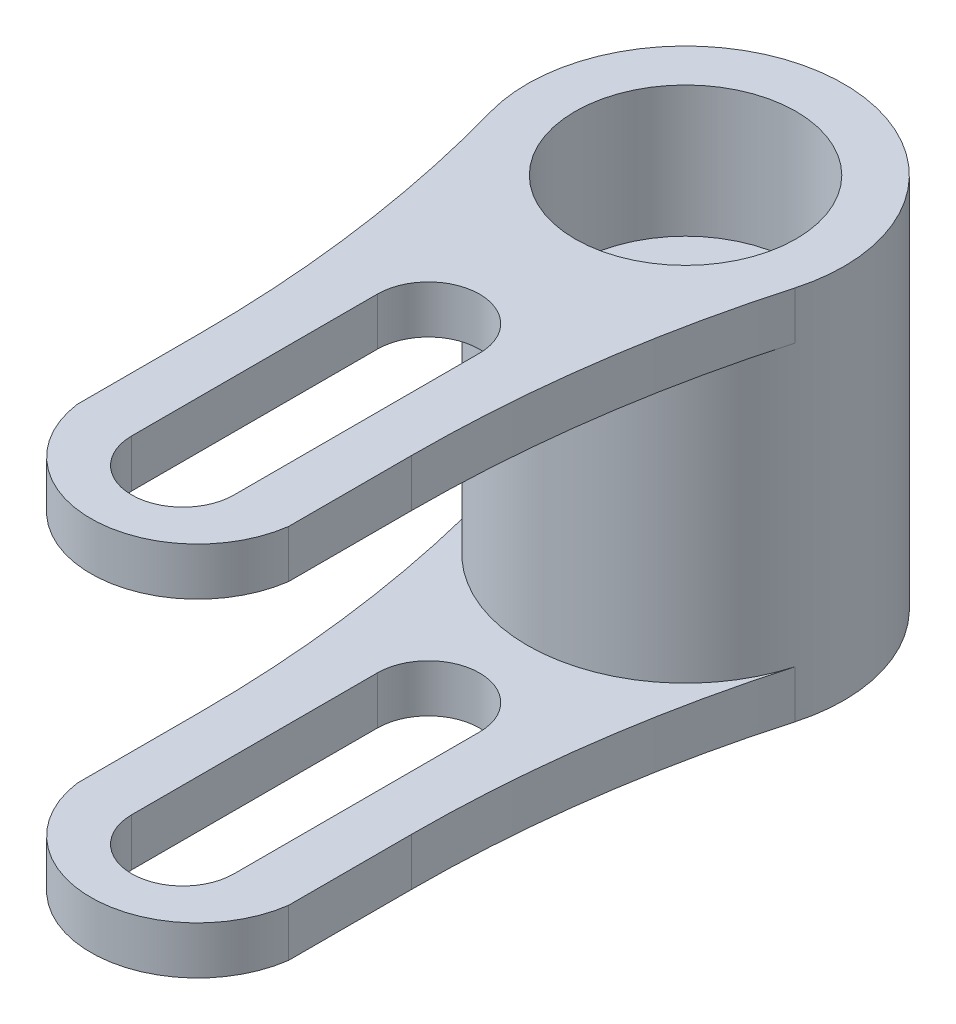
SolidWorks part; units mm, degrees
ref_plane "Front Plane" through (0, 0, 0) normal (0, 0, 1) x (1, 0, 0)
ref_plane "Top Plane" through (0, 0, 0) normal (0, 1, 0) x (1, 0, 0)
ref_plane "Right Plane" through (0, 0, 0) normal (1, 0, 0) x (0, 0, -1)
sketch "Sketch1" plane through (0, 0, 0) normal (0, 1, 0) x (1, 0, 0)
  line L0 (0, 5.8) -> (0, 4.05) construction
  line L1 (0, -9.425) -> (0, -18.425) construction
  line L2 (-3.875, -13.925) -> (-3.875, -18.425)
  line L3 (3.875, -18.425) -> (3.875, -13.925)
  line L4 (1.875, -9.425) -> (1.875, -18.425)
  line L5 (-1.875, -9.425) -> (-1.875, -18.425)
  line L6 (0, -7.55) -> (0, -5.8) construction
  line L7 (-3.875, -13.925) -> (3.875, -13.925) construction
  circle A0 centre (0, 0) radius 4.05
  circle A1 centre (0, 0) radius 5.8
  arc A2 (1.875, -9.425) -> (-1.875, -9.425) centre (0, -9.425) ccw
  arc A3 (-5.5825, -1.5735) -> (-3.875, -13.925) centre (-49.4026, -13.925) cw
  arc A4 (-3.875, -18.425) -> (3.875, -18.425) centre (0, -18.425) ccw
  arc A5 (3.875, -13.925) -> (5.5825, -1.5735) centre (49.4026, -13.925) cw
  arc A6 (-1.875, -18.425) -> (1.875, -18.425) centre (0, -18.425) ccw
  point P6 (0, -13.925)
  dimension "D1" = 8.1
  dimension "D2" = 1.75
  dimension "D3" = 3.75
  dimension "D4" = 2
  dimension "D5" = 9
  dimension "D6" = 1.75
extrude "Boss-Extrude1" add sketch "Sketch1" along normal mid plane 13.775 contours L3 A5 A1 A3 L2 A4 A6 L5 A2 L4 | A0 | A1 A0 region at (-4.0707, 0, 7.6583) region at (-0.7718, 0, -5.5829) region at (0, 0, 0)
ref_plane "Plane1" through (0, -5.1375, 0) normal (0, -1, 0) x (-1, 0, 0)
ref_plane "Plane2" through (0, 5.1375, 0) normal (0, 1, 0) x (1, 0, 0)
extrude "Cut-Extrude1" cut sketch "Sketch1<4>" along normal up to surface (10.275 mm away) from surface contours L3 A5 A1 A3 L2 A4 A6 L5 A2 L4 region at (-4.0707, 0, 7.6583) up to plane "Plane2" starting at plane "Plane1"
sketch "Sketch1<4>" plane through (0, 0, 0) normal (0, 1, 0) x (1, 0, 0) same geometry as "Sketch1"
extrude "Cut-Extrude2" cut sketch "Sketch1<5>" against normal blind 4.8 from surface contours A0 region at (0, 0, 0) starting at face at (0, 6.8875, 13.925)
sketch "Sketch1<5>" plane through (0, 0, 0) normal (0, 1, 0) x (1, 0, 0) same geometry as "Sketch1"
sketch "Sketch4" plane through (0, -6.8875, 0) normal (0, -1, 0) x (1, 0, 0)
  line L2 (0, 21.8) -> (0, 22.3) construction
  line L4 (0, 21.8) -> (0, 20.3) construction
  arc A0 (3.875, 18.425) -> (-3.875, 18.425) centre (0, 18.425) ccw construction
  arc A1 (1.875, 18.425) -> (-1.875, 18.425) centre (0, 18.425) ccw construction
  arc A3 (-3.875, 18.425) -> (3.875, 18.425) centre (0, 17.888) cw
  arc A4 (3.875, 18.425) -> (-3.875, 18.425) centre (0, 18.425) ccw
  dimension "D1" = 0.5
extrude "Cut-Extrude3" cut sketch "Sketch4" against normal through all
equation "\"D1@Boss-Extrude1\"=9.525mm+1.75mm+1.75mm+.75mm"
